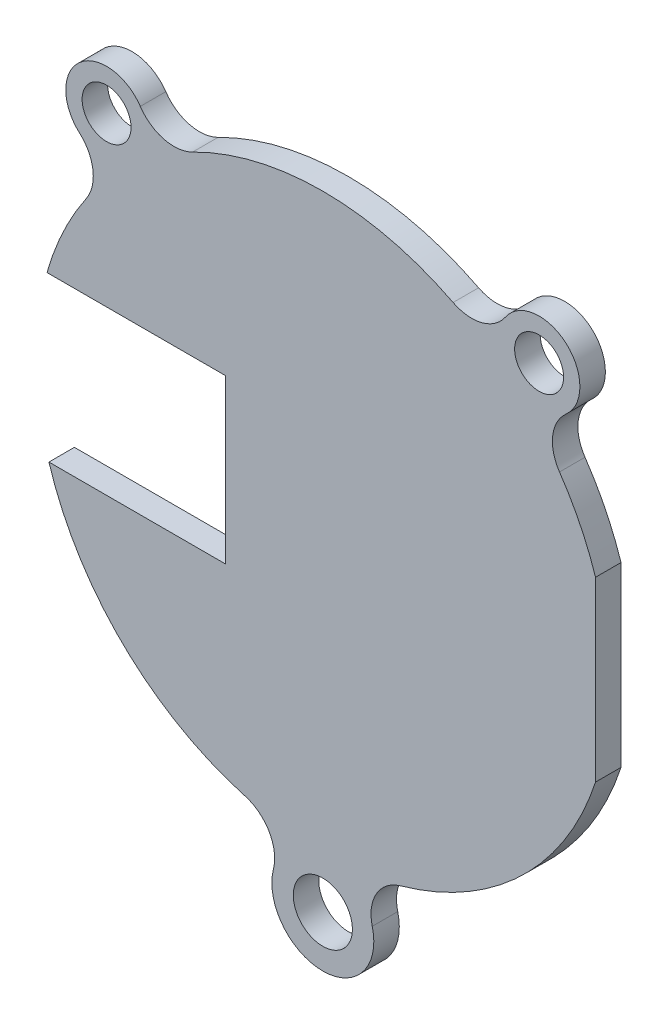
SolidWorks part; units mm, degrees
ref_plane "Front Plane" through (0, 0, 0) normal (0, 0, 1) x (1, 0, 0)
ref_plane "Top Plane" through (0, 0, 0) normal (0, 1, 0) x (1, 0, 0)
ref_plane "Right Plane" through (0, 0, 0) normal (1, 0, 0) x (0, 0, -1)
sketch "Sketch1" plane through (0, 0, 0) normal (0, 0, 1) x (1, 0, 0)
  line L0 (-6.0563, 4.8768) -> (-17.1812, 4.8768) construction
  line L2 (-17.0607, -5.2832) -> (-6.0563, -5.2832) construction
  line L5 (16.9841, -5.5245) -> (16.9841, 5.5245) construction
  line L10 (-6.0563, 4.8768) -> (-17.1812, 4.8768)
  line L11 (-6.0563, 4.8768) -> (-6.0563, -5.2832)
  line L12 (-17.0607, -5.2832) -> (-6.0563, -5.2832)
  line L15 (16.9841, -5.5245) -> (16.9841, 5.5245)
  arc A0 (-17.0607, -5.2832) -> (-4.8506, -17.1887) centre (0, 0) ccw construction
  arc A3 (4.8506, -17.1887) -> (16.9841, -5.5245) centre (0, 0) ccw construction
  arc A4 (16.9841, 5.5245) -> (14.7417, 10.0827) centre (0, 0) ccw construction
  arc A8 (-14.7417, 10.0827) -> (-17.1812, 4.8768) centre (0, 0) ccw construction
  arc A9 (-17.0607, -5.2832) -> (-4.8506, -17.1887) centre (0, 0) ccw
  arc A10 (4.8506, -17.1887) -> (3.078, -20.2562) centre (5.5404, -19.6332) ccw construction
  arc A11 (-3.078, -20.2562) -> (3.078, -20.2562) centre (0, -21.035) ccw construction
  arc A12 (4.8506, -17.1887) -> (16.9841, -5.5245) centre (0, 0) ccw
  arc A13 (16.9841, 5.5245) -> (14.7417, 10.0827) centre (0, 0) ccw
  arc A14 (-3.078, -20.2562) -> (-4.8506, -17.1887) centre (-5.5404, -19.6332) ccw construction
  arc A15 (8.1137, 15.9106) -> (-8.1137, 15.9106) centre (0, 0) ccw
  arc A16 (-14.7417, 10.0827) -> (-15.1544, 13.4183) centre (-16.8382, 11.5166) ccw construction
  arc A17 (-14.7417, 10.0827) -> (-17.1812, 4.8768) centre (0, 0) ccw
  arc A20 (-11.3691, 16.7466) -> (-15.1544, 13.4183) centre (-13.4706, 15.32) ccw construction
  arc A21 (-11.3691, 16.7466) -> (-8.1137, 15.9106) centre (-9.2677, 18.1733) ccw construction
  arc A22 (8.1137, 15.9106) -> (11.3691, 16.7466) centre (9.2677, 18.1733) ccw construction
  arc A23 (15.1544, 13.4183) -> (11.3691, 16.7466) centre (13.4706, 15.32) ccw construction
  arc A24 (15.1544, 13.4183) -> (14.7417, 10.0827) centre (16.8382, 11.5166) ccw construction
  arc A25 (4.8506, -17.1887) -> (3.078, -20.2562) centre (5.5404, -19.6332) ccw
  arc A26 (-3.078, -20.2562) -> (3.078, -20.2562) centre (0, -21.035) ccw
  arc A27 (-3.078, -20.2562) -> (-4.8506, -17.1887) centre (-5.5404, -19.6332) ccw
  arc A28 (-14.7417, 10.0827) -> (-15.1544, 13.4183) centre (-16.8382, 11.5166) ccw
  arc A29 (-11.3691, 16.7466) -> (-15.1544, 13.4183) centre (-13.4706, 15.32) ccw
  arc A30 (-11.3691, 16.7466) -> (-8.1137, 15.9106) centre (-9.2677, 18.1733) ccw
  arc A31 (8.1137, 15.9106) -> (11.3691, 16.7466) centre (9.2677, 18.1733) ccw
  arc A32 (15.1544, 13.4183) -> (11.3691, 16.7466) centre (13.4706, 15.32) ccw
  arc A33 (15.1544, 13.4183) -> (14.7417, 10.0827) centre (16.8382, 11.5166) ccw
  circle A34 centre (0, -21.035) radius 1.8415 construction
  circle A35 centre (13.4706, 15.32) radius 1.524 construction
  circle A36 centre (-13.4706, 15.32) radius 1.524 construction
  circle A37 centre (0, -21.035) radius 1.8415
  circle A38 centre (13.4706, 15.32) radius 1.524
  circle A39 centre (-13.4706, 15.32) radius 1.524
extrude "Boss-Extrude1" add sketch "Sketch1" along normal blind 1.5875
